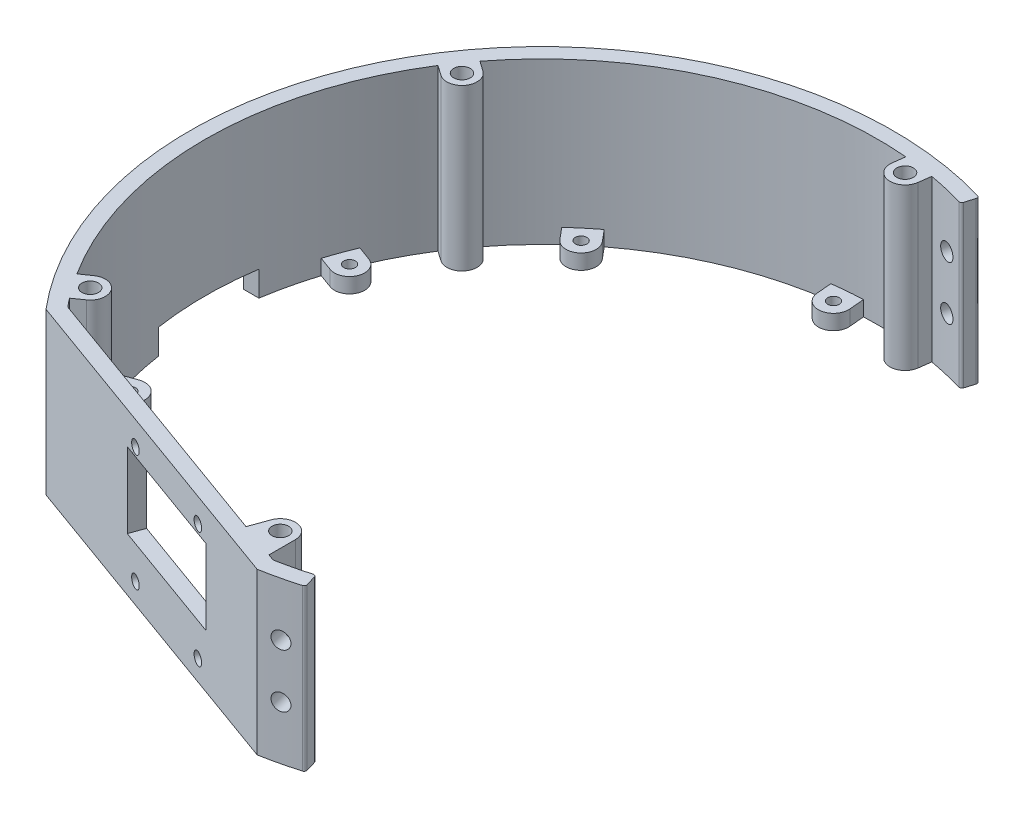
SolidWorks part; units mm, degrees
ref_plane "Front Plane" through (0, 0, 0) normal (0, 0, 1) x (1, 0, 0)
ref_plane "Top Plane" through (0, 0, 0) normal (0, 1, 0) x (1, 0, 0)
ref_plane "Right Plane" through (0, 0, 0) normal (1, 0, 0) x (0, 0, -1)
sketch "Sketch2" plane through (0, 0, 0) normal (0, 1, 0) x (1, 0, 0)
  line L0 (12.3, 68.9109) -> (12.3, -68.9109) construction
  line L1 (12.3, -68.9109) -> (-53.5286, -45.1076)
  line L3 (-51.7436, -42.5629) -> (12.3, -65.7208)
  line L4 (20.0782, 67.0587) -> (0, 0) construction
  line L5 (0, 0) -> (20.0782, -67.0587) construction
  line L6 (19.2177, 64.1847) -> (20.0782, 67.0587)
  line L7 (20.0782, -67.0587) -> (19.178, -64.0524)
  arc A0 (12.3, 68.9109) -> (12.3, -68.9109) centre (0, 0) ccw construction
  arc A1 (-53.5286, -45.1076) -> (12.3, 68.9109) centre (0, 0) cw
  arc A2 (12.3, 65.8613) -> (-51.7436, -42.5629) centre (0, 0) ccw
  arc A3 (12.3, 68.9109) -> (20.0782, 67.0587) centre (0, 0) cw
  arc A4 (12.3, 65.8613) -> (19.2177, 64.1847) centre (0, 0) cw
  arc A5 (12.3, -68.9109) -> (20.0782, -67.0587) centre (0, 0) ccw
  arc A6 (12.3, -65.7208) -> (19.178, -64.0524) centre (0, 0) ccw
  dimension "D1" = 70
  dimension "D4" = 3
  dimension "D6" = 8
  dimension "D2" = 12.3
  dimension "D3" = 3
  dimension "D5" = 70
  dimension "D7" = 8
extrude "Boss-Extrude1" add sketch "Sketch2" along normal blind 32
sketch "Sketch3" plane through (0, 0, 0) normal (0, 1, 0) x (1, 0, 0)
  line L0 (12.3, 68.9109) -> (12.3, -68.9109) construction
  line L1 (20.0782, -67.0587) -> (19.178, -64.0524) construction
  line L2 (19.2177, 64.1847) -> (20.0782, 67.0587) construction
  circle A0 centre (0, 0) radius 70 construction
  arc A1 (12.3, -68.9109) -> (20.0782, -67.0587) centre (0, 0) ccw
  arc A2 (12.3, 68.9109) -> (20.0782, 67.0587) centre (0, 0) cw
  point P8 (16.2155, -68.0959)
  point P9 (16.2155, 68.0959)
  dimension "D2" = 140
  dimension "D1" = 12.3
sketch3d "3DSketch1"
  line L0 (16.2155, 0, 68.0959) -> (16.2155, 32, 68.0959)
  line L1 (16.2155, 0, -68.0959) -> (16.2155, 32, -68.0959)
  arc A0 (12.3, 32, 68.9109) -> (20.0782, 32, 67.0587) centre (0, 32, 0) ccw construction
  arc A1 (20.0782, 32, -67.0587) -> (-53.5286, 32, 45.1076) centre (0, 32, 0) ccw construction
  point P6 (0, 102, 0)
  point P13 (0, 102, 0)
ref_plane "Plane1" through (16.2155, 0, -68.0959) normal (0.2317, 0, -0.9728) x (-0.9728, 0, -0.2317)
ref_plane "Plane2" through (16.2155, 0, 68.0959) normal (0.2317, 0, 0.9728) x (0.9728, 0, -0.2317)
sketch "Sketch4" plane through (16.2155, 0, -68.0959) normal (0.2317, 0, -0.9728) x (-0.9728, 0, -0.2317)
  line L0 (0, 0) -> (0, 32) construction
  circle A0 centre (0, 21.3333) radius 1.65
  circle A1 centre (0, 10.6667) radius 1.65
  dimension "D1" = 3.3
  dimension "D2" = 10.6667
  dimension "D3" = 21.3333
extrude "Cut-Extrude1" cut sketch "Sketch4" against normal blind 32
sketch "Sketch5" plane through (16.2155, 0, 68.0959) normal (0.2317, 0, 0.9728) x (0.9728, 0, -0.2317)
  line L0 (0, 0) -> (0, 32) construction
  circle A0 centre (0, 21.3333) radius 1.65
  circle A1 centre (0, 10.6667) radius 1.65
  dimension "D1" = 3.3
  dimension "D2" = 10.6667
  dimension "D3" = 21.3333
extrude "Cut-Extrude2" cut sketch "Sketch5" against normal blind 32
fillet "Fillet1" radius 0.5 4 edges at (20.0782, 16, -67.0587) (19.2177, 16, -64.1847) (19.178, 16, 64.0524) (20.0782, 16, 67.0587)
sketch "Sketch6" plane through (0, 0, 0) normal (1, 0, 0) x (0, 0, -1)
  line L0 (70, 0) -> (-70, 0) construction
  line L1 (-10, 0) -> (10, 0)
  line L2 (-10, 0) -> (-10, 5)
  line L3 (-10, 5) -> (10, 5)
  line L4 (10, 0) -> (10, 5)
  dimension "D1" = 10
  dimension "D2" = 5
  dimension "D3" = 20
extrude "Cut-Extrude3" cut sketch "Sketch6" against normal through all
sketch "Sketch7" plane through (-20.6143, 0, 57.0092) normal (-0.34, 0, 0.9404) x (0.9404, 0, 0.34)
  line L0 (5, 29.3) -> (5, 2) construction
  line L1 (-8.65, 29.3) -> (18.65, 29.3) construction
  line L2 (-8.65, 29.3) -> (-8.65, 2) construction
  line L3 (-8.65, 2) -> (18.65, 2) construction
  line L4 (18.65, 29.3) -> (18.65, 2) construction
  line L5 (-8.65, 29.3) -> (18.65, 2) construction
  line L6 (-8.65, 2) -> (18.65, 29.3) construction
  line L7 (-35, 0) -> (35, 0) construction
  line L8 (-8.05, 25.58) -> (18.05, 25.58)
  line L9 (-8.05, 25.58) -> (-8.05, 10.58)
  line L10 (-8.05, 10.58) -> (18.05, 10.58)
  line L11 (18.05, 25.58) -> (18.05, 10.58)
  line L12 (-8.05, 25.58) -> (18.05, 10.58) construction
  line L13 (-8.05, 10.58) -> (18.05, 25.58) construction
  line L14 (-5.35, 27.25) -> (15.35, 27.25) construction
  line L15 (-5.35, 27.25) -> (-5.35, 4.05) construction
  line L16 (-5.35, 4.05) -> (15.35, 4.05) construction
  line L17 (15.35, 27.25) -> (15.35, 4.05) construction
  circle A0 centre (-5.35, 27.25) radius 1.25
  circle A1 centre (15.35, 27.25) radius 1.25
  circle A2 centre (15.35, 4.05) radius 1.25
  circle A3 centre (-5.35, 4.05) radius 1.25
  point P0 (5, 15.65)
  point P5 (5, 18.08)
  point P24 (0, 0)
  dimension "D9" = 2.5
  dimension "D1" = 27.3
  dimension "D2" = 27.3
  dimension "D3" = 26.1
  dimension "D4" = 15
  dimension "D5" = 2.05
  dimension "D6" = 3.3
  dimension "D7" = 20.7
  dimension "D8" = 11.22
  dimension "D10" = 5
  dimension "D11" = 2
  dimension "D12" = 23.2
extrude "Cut-Extrude4" cut sketch "Sketch7" against normal blind 8
sketch "Sketch8" plane through (0, 0, 0) normal (0, 1, 0) x (1, 0, 0)
  line L0 (8.7453, 66.4268) -> (8.4189, 63.9482) construction
  line L1 (11.7108, 65.9686) -> (11.3933, 63.5566)
  line L2 (5.7621, 66.7518) -> (5.4446, 64.3398)
  line L3 (5.4446, 64.3398) -> (11.3933, 63.5566) construction
  line L4 (-54.8832, 38.4296) -> (-52.8353, 36.9957) construction
  line L5 (-53.1074, 40.8485) -> (-51.1146, 39.4531)
  line L6 (-56.5489, 35.9336) -> (-54.556, 34.5382)
  line L7 (-54.556, 34.5382) -> (-51.1146, 39.4531) construction
  line L8 (-54.8832, -38.4296) -> (-52.8353, -36.9957) construction
  line L9 (-56.5489, -35.9336) -> (-54.556, -34.5382)
  line L10 (-53.1074, -40.8485) -> (-51.1146, -39.4531)
  line L11 (-51.1146, -39.4531) -> (-54.556, -34.5382) construction
  line L12 (0, 1.3173) -> (0, 50001.3173) construction
  line L13 (11, -65.2507) -> (11, -60)
  line L14 (12.3, -65.7208) -> (-51.7436, -42.5629) construction
  line L15 (5.1788, -58.9799) -> (3.8466, -62.6641)
  line L16 (8, -60) -> (6.6678, -63.6842) construction
  line L17 (11, -65.2507) -> (3.8466, -62.6641)
  arc A0 (-53.1074, -40.8485) -> (-56.5489, -35.9336) centre (0, 0) cw
  arc A1 (18.7417, 64.3253) -> (-51.7436, -42.5629) centre (0, 0) ccw construction
  arc A2 (5.7621, 66.7518) -> (11.7108, 65.9686) centre (0, 0) cw
  circle A3 centre (8.4189, 63.9482) radius 1.65
  arc A4 (11.3933, 63.5566) -> (5.4446, 64.3398) centre (8.4189, 63.9482) cw
  arc A5 (-56.5489, 35.9336) -> (-53.1074, 40.8485) centre (0, 0) cw
  circle A6 centre (-52.8353, 36.9957) radius 1.65
  arc A7 (-51.1146, 39.4531) -> (-54.556, 34.5382) centre (-52.8353, 36.9957) cw
  circle A8 centre (-52.8353, -36.9957) radius 1.65
  arc A9 (-54.556, -34.5382) -> (-51.1146, -39.4531) centre (-52.8353, -36.9957) cw
  arc A10 (11, -60) -> (5.1788, -58.9799) centre (8, -60) ccw
  circle A11 centre (8, -60) radius 1.65
  circle A12 centre (0, 0) radius 67 construction
  point P12 (8.7453, 66.4268)
  point P15 (8.7453, 66.4268)
  point P17 (8.4189, 63.9482)
  point P24 (-54.8832, 38.4296)
  point P26 (-54.8832, 38.4296)
  point P27 (-52.8353, 36.9957)
  point P43 (-52.8353, -36.9957)
  dimension "D1" = 3.3
  dimension "D2" = 6
  dimension "D3" = 3.3
  dimension "D5" = 3.3
  dimension "D13" = 3
  dimension "D14" = 3.3
  dimension "D4" = 6
  dimension "D6" = 6
  dimension "D7" = 2.5
  dimension "D8" = 7.5
  dimension "D9" = 55
  dimension "D10" = 55
  dimension "D11" = 2.5
  dimension "D12" = 2.5
  dimension "D15" = 60
  dimension "D16" = 8
extrude "Boss-Extrude2" add sketch "Sketch8" along normal up to surface (32 mm away) up to face at (-0.5146, 32, 14.0886)
sketch "Sketch13" plane through (0, 0, 0) normal (0, 1, 0) x (1, 0, 0)
  line L0 (-62.8963, 22.8924) -> (-60.0772, 21.8663) construction
  line L1 (-59.0511, 24.6854) -> (-61.1032, 19.0472) construction
  line L2 (-61.1032, 19.0472) -> (-63.9223, 20.0733)
  line L3 (-61.8702, 25.7114) -> (-59.0511, 24.6854)
  line L4 (0, 0) -> (0, 50000) construction
  line L5 (-62.8963, -22.8924) -> (-60.0772, -21.8663) construction
  line L6 (-61.1032, -19.0472) -> (-59.0511, -24.6854) construction
  line L7 (-59.0511, -24.6854) -> (-61.8702, -25.7114)
  line L8 (-63.9223, -20.0733) -> (-61.1032, -19.0472)
  line L9 (-5.8336, 66.6781) -> (-5.5721, 63.6895) construction
  line L10 (-2.5835, 63.951) -> (-8.5607, 63.4281) construction
  line L11 (-8.5607, 63.4281) -> (-8.8222, 66.4166)
  line L12 (-2.845, 66.9396) -> (-2.5835, 63.951)
  line L13 (-43.0236, 51.2735) -> (-41.0952, 48.9754) construction
  line L14 (-38.7971, 50.9037) -> (-43.3933, 47.047) construction
  line L15 (-43.3933, 47.047) -> (-45.3217, 49.3451)
  line L16 (-40.7254, 53.2019) -> (-38.7971, 50.9037)
  line L17 (1.0254, -61.6439) -> (2.0455, -58.8227) construction
  line L18 (-0.7757, -57.8026) -> (4.8667, -59.8428) construction
  line L19 (4.8667, -59.8428) -> (3.8466, -62.6641)
  line L20 (-1.7959, -60.6238) -> (-0.7757, -57.8026)
  line L21 (3.8466, -62.6641) -> (-1.7959, -60.6238)
  line L22 (5.1788, -58.9799) -> (3.8466, -62.6641) construction
  line L25 (3.8466, -62.6641) -> (-51.7436, -42.5629) construction
  circle A0 centre (0, 0) radius 67 construction
  arc A1 (-63.9223, 20.0733) -> (-61.8702, 25.7114) centre (0, 0) cw
  arc A2 (-61.1032, 19.0472) -> (-59.0511, 24.6854) centre (-60.0772, 21.8663) ccw
  circle A3 centre (-60.0772, 21.8663) radius 1.15
  arc A4 (-61.8702, -25.7114) -> (-63.9223, -20.0733) centre (0, 0) cw
  arc A5 (-59.0511, -24.6854) -> (-61.1032, -19.0472) centre (-60.0772, -21.8663) ccw
  circle A6 centre (-60.0772, -21.8663) radius 1.15
  arc A7 (-8.8222, 66.4166) -> (-2.845, 66.9396) centre (0, 0) cw
  arc A8 (-8.5607, 63.4281) -> (-2.5835, 63.951) centre (-5.5721, 63.6895) ccw
  circle A9 centre (-5.5721, 63.6895) radius 1.15
  arc A10 (-45.3217, 49.3451) -> (-40.7254, 53.2019) centre (0, 0) cw
  arc A11 (-43.3933, 47.047) -> (-38.7971, 50.9037) centre (-41.0952, 48.9754) ccw
  circle A12 centre (-41.0952, 48.9754) radius 1.15
  arc A14 (4.8667, -59.8428) -> (-0.7757, -57.8026) centre (2.0455, -58.8227) ccw
  circle A15 centre (2.0455, -58.8227) radius 1.15
  point P10 (-60.0772, 21.8663)
  point P20 (-60.0772, -21.8663)
  point P22 (0, 0)
  point P30 (-5.5721, 63.6895)
  point P32 (-11.1643, -55.924)
  point P41 (-41.0952, 48.9754)
  point P43 (-10.528, -51.4211)
  point P45 (1.5889, -58.6576)
  point P52 (2.0455, -58.8227)
  point P56 (4.8667, -59.8428)
  point P59 (-5.0633, -7.0394)
  dimension "D1" = 134
  dimension "D2" = 3
  dimension "D3" = 2.3
  dimension "D6" = 3
  dimension "D7" = 2.3
  dimension "D10" = 3
  dimension "D11" = 2.3
  dimension "D14" = 3
  dimension "D15" = 2.3
  dimension "D18" = 3
  dimension "D19" = 2.3
  dimension "D4" = 3
  dimension "D5" = 70
  dimension "D8" = 3
  dimension "D9" = 70
  dimension "D12" = 3
  dimension "D13" = 5
  dimension "D16" = 3
  dimension "D17" = 40
  dimension "D20" = 3
  dimension "D21" = 2.0455
  dimension "D22" = 58.8227
extrude "Boss-Extrude3" add sketch "Sketch13" along normal blind 3
